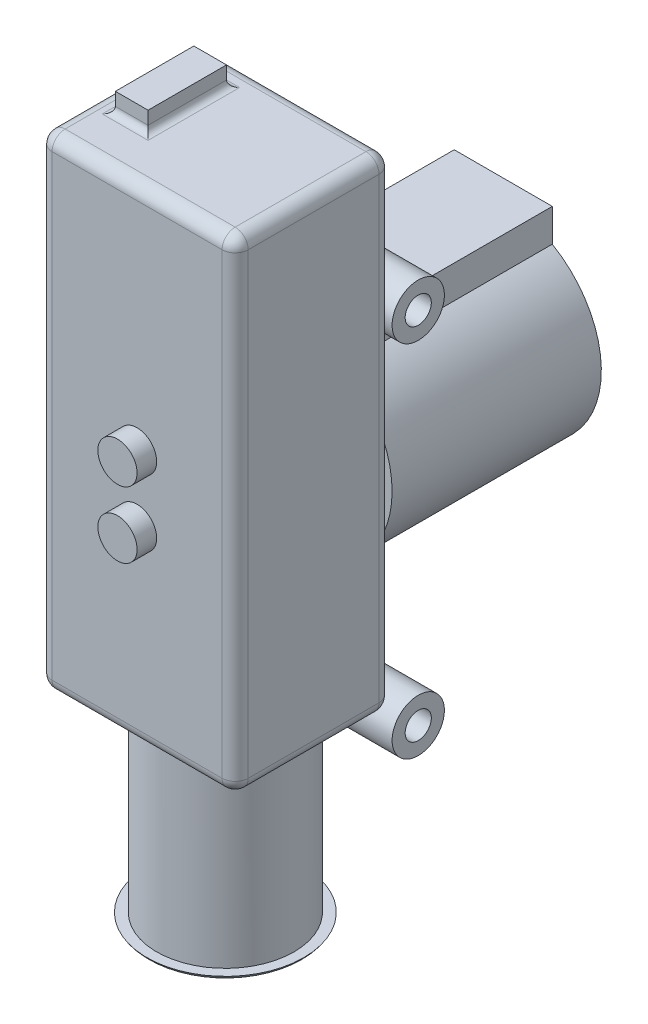
SolidWorks part; units mm, degrees
ref_plane "Plan de face" through (0, 0, 0) normal (0, 0, 1) x (1, 0, 0)
ref_plane "Plan de dessus" through (0, 0, 0) normal (0, 1, 0) x (1, 0, 0)
ref_plane "Plan de droite" through (0, 0, 0) normal (1, 0, 0) x (0, 0, -1)
sketch "Esquisse1" plane through (0, 0, 0) normal (0, 0, 1) x (1, 0, 0)
  line L0 (-15, -28.7954) -> (15, -28.7954)
  line L1 (15, -28.7954) -> (15, 45.2046)
  line L2 (15, 45.2046) -> (-15, 45.2046)
  line L3 (0, 60.8191) -> (0, -53.0714) construction
  line L4 (-15, -28.7954) -> (-15, 45.2046)
  point P8 (0, -28.7954)
  point P9 (0, 45.2046)
  dimension "D1" = 15
  dimension "D2" = 74
extrude "Boss.-Extru.1" add sketch "Esquisse1" along normal blind 24
sketch "Esquisse2" plane through (0, -28.7954, 0) normal (0, -1, 0) x (1, 0, 0)
  line L0 (-15, 24) -> (15, 0) construction
  line L1 (-15, 0) -> (15, 0) construction
  circle A0 centre (0, 10.5) radius 10.5
  point P9 (0, 12)
  dimension "D1" = 21
extrude "Boss.-Extru.2" add sketch "Esquisse2" along normal blind 29
sketch "Esquisse3" plane through (0, -57.7954, 0) normal (0, -1, 0) x (1, 0, 0)
  circle A0 centre (0, 10.5) radius 12
  circle A1 centre (0, 10.5) radius 3.5
  dimension "D1" = 24
  dimension "D2" = 7
extrude "Boss.-Extru.3" add sketch "Esquisse3" along normal blind 1
extrude "Enlèv. mat.-Extru.1" cut sketch "Esquisse3<3>" against normal blind 55 contours A1 region at (0, -57.7954, 10.5)
sketch "Esquisse3<3>" plane through (0, -57.7954, 0) normal (0, -1, 0) x (1, 0, 0) same geometry as "Esquisse3"
fillet "Congé1" radius 2 14 edges at (-7.5, -28.7954, 0) (12, -58.7954, 10.5) (7.5, -28.7954, 0) (15, -28.7954, 12) (0, -28.7954, 24) (-15, -28.7954, 12) (0, 45.2046, 0) (0, 45.2046, 24) (-15, 45.2046, 12) (15, 45.2046, 12) (15, 8.2046, 0) (-15, 8.2046, 0) (-15, 8.2046, 24) (15, 8.2046, 24)
sketch "Esquisse4" plane through (0, 0, 0) normal (0, 0, -1) x (-1, 0, 0)
  line L0 (7.5, 18.2046) -> (-7.5, 18.2046)
  line L1 (-13, 45.2046) -> (13, 45.2046) construction
  line L3 (-15, -26.7954) -> (-15, 43.2046) construction
  line L4 (-7.5, 18.2046) -> (-7.5, 13.1949)
  line L5 (0, 18.2046) -> (0, -11.7469) construction
  line L6 (7.5, 18.2046) -> (7.5, 13.1949)
  circle A0 centre (0, 0.2046) radius 15
  line M3 (-13, 43.2046) -> (-13, -26.7954)
  line M8 (13, -26.7954) -> (13, 43.2046)
  dimension "D3" = 18
  dimension "D4" = 30
  dimension "D1" = 27
  dimension "D2" = 7.5
extrude "Boss.-Extru.4" add sketch "Esquisse4" along normal blind 32 contours A0 M8 | A0 M8 M3 | A0 M3 | L5 L0 L4 A0 | L0 L5 A0 L6 region at (-4.0889, 16.331, 0) region at (4.0889, 16.331, 0) region at (-10.3325, 10.5238, 0) region at (-13.8048, 0.2046, 0) region at (13.8048, 0.2046, 0)
sketch "Esquisse5" plane through (-15, 0, 0) normal (-1, 0, 0) x (0, 0, 1)
  line L0 (0, -26.7954) -> (0, -7.2788) construction
  line L1 (0, 7.6879) -> (0, 43.2046) construction
  line L2 (-32, 18.2046) -> (0, 18.2046) construction
  circle A0 centre (-4, -32.7954) radius 4
  circle A1 centre (-4, -32.7954) radius 2
  circle A2 centre (-4, 22.2046) radius 4
  circle A3 centre (-4, 22.2046) radius 2
  dimension "D1" = 8
  dimension "D2" = 4
  dimension "D3" = 8
  dimension "D4" = 4
  dimension "D5" = 55
extrude "Boss.-Extru.5" add sketch "Esquisse5" against normal blind 30 separate body contours A2 A3 | A0 | A1 region at (-15, 22.2046, -7.8869)
sketch "Esquisse6" plane through (0, 0, 24) normal (0, 0, 1) x (1, 0, 0)
  circle A0 centre (0, 0) radius 3
  circle A1 centre (0, 10.1371) radius 3
  dimension "D1" = 6
  dimension "D2" = 6
extrude "Boss.-Extru.6" add sketch "Esquisse6" along normal blind 3
sketch "Esquisse7" plane through (0, 45.2046, 0) normal (0, 1, 0) x (1, 0, 0)
  line L1 (-6.1496, -16.1707) -> (-11.1496, -16.1707)
  line L2 (-6.1496, -16.1707) -> (-6.1496, -4.1707)
  line L3 (-6.1496, -4.1707) -> (-11.1496, -4.1707)
  line L4 (-11.1496, -16.1707) -> (-11.1496, -4.1707)
  dimension "D1" = 5
  dimension "D2" = 12
extrude "Boss.-Extru.7" add sketch "Esquisse7" along normal blind 3
fillet "Congé2" radius 1 4 edges at (-8.6496, 45.2046, 4.1707) (-11.1496, 45.2046, 10.1707) (-8.6496, 45.2046, 16.1707) (-6.1496, 45.2046, 10.1707)
